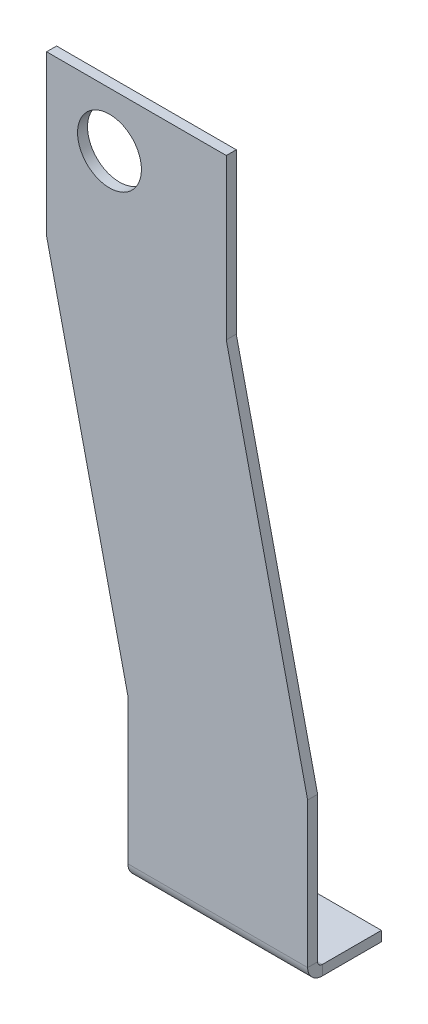
SolidWorks part; units mm, degrees
note: The reader was unsure of these and kept them because the rebuilt part matched: flange length of "Edge-Flange1".
material "Copper"
ref_plane "Front Plane" through (0, 0, 0) normal (0, 0, 1) x (1, 0, 0)
ref_plane "Top Plane" through (0, 0, 0) normal (0, 1, 0) x (1, 0, 0)
ref_plane "Right Plane" through (0, 0, 0) normal (1, 0, 0) x (0, 0, -1)
sketch "Sketch1" plane through (0, 0, 0) normal (0, 0, 1) x (1, 0, 0)
  line L0 (0, -25.4) -> (12.9388, -82.3036)
  line L1 (0, 0) -> (28.575, 0)
  line L2 (0, 0) -> (0, -25.4)
  line L3 (12.9388, -82.3036) -> (12.9388, -107.7036)
  line L4 (28.575, 0) -> (28.575, -25.4)
  line L5 (41.5138, -82.3036) -> (28.575, -25.4)
  line L6 (12.9388, -107.7036) -> (41.5138, -107.7036)
  line L7 (41.5138, -107.7036) -> (41.5138, -82.3036)
  circle A0 centre (10, -8.6741) radius 5.08
  dimension "D5" = 10.16
  dimension "D1" = 28.575
  dimension "D2" = 12.9388
  dimension "D3" = 107.7036
  dimension "D4" = 8.6741
  dimension "D6" = 25.4
  dimension "D7" = 25.4
  dimension "D8" = 10
base flange "Base-Flange1" sketch "Sketch1" thickness 1.5875 reverse thickness direction no parameters "D1"=0.7366
edge flange "Edge-Flange1" sketch "Sketch8" flange angle 90 flange length 11.7297 flange position material inside bend radius 0.7366 thickness 1.5875 relief rectangular parameters "D6"=10
sketch "Sketch8" plane through (0, -107.7036, -1.5875) normal (0, -1, 0) x (-1, 0, 0)
  line L0 (-12.9388, 0) -> (-41.5138, 0) construction
  line L1 (-12.9388, 0) -> (-41.5138, 0)
  line L2 (-41.5138, 0) -> (-41.5138, 10.1422)
  line L3 (-41.5138, 10.1422) -> (-12.9388, 10.1422)
  line L4 (-12.9388, 10.1422) -> (-12.9388, 0)
bend "EdgeBend1" bend radius 0.7366 bend angle 90 parameters "D5"=1
sketch "Bend-Lines1" [suppressed] plane through (0, 0, 0) normal (0, 1, 0) x (1, 0, 0)
sketch "Bounding-Box1" [suppressed] plane through (0, 0, 0) normal (0, 1, 0) x (1, 0, 0)
sheet metal parameters "Sheet-Metal1" thickness 1.5875 parameters "D1"=0.7366
flat pattern "Flat-Pattern1" [suppressed]
sketch "Bend-Lines2" plane through (0, 0, 0) normal (0, 1, 0) x (1, 0, 0)
sketch3d "Bounding-Box2" [suppressed]
  line L0 (-27.8858, 4.3839, 0) -> (-45.4105, -107.091, 0) construction
  line L1 (3.8968, -0.6126, 0) -> (-13.6279, -112.0875, 0) construction
  line L2 (-27.8858, 4.3839, 0) -> (3.8968, -0.6126, 0) construction
  line L3 (-45.4105, -107.091, 0) -> (-13.6279, -112.0875, 0) construction
sheet metal parameters "Sheet-Metal2" thickness 1.5875 parameters "D1"=0.7366
flat pattern "Flat-Pattern1"
sketch "Bend-Lines2" plane through (0, 0, 0) normal (0, 0, 1) x (1, 0, 0)
  line L0 (12.9388, -106.5815) -> (41.5138, -106.5815) construction
  line L1 (12.9388, -106.5815) -> (41.5138, -106.5815) construction
sketch3d "Bounding-Box2" [suppressed]
  line L0 (29.3293, 4.1343, 0) -> (46.3355, -116.5093, 0) construction
  line L1 (-3.5107, -0.4949, 0) -> (13.4955, -121.1385, 0) construction
  line L2 (29.3293, 4.1343, 0) -> (-3.5107, -0.4949, 0) construction
  line L3 (46.3355, -116.5093, 0) -> (13.4955, -121.1385, 0) construction
bend of the flat pattern "Flatten-<EdgeBend1>1"
